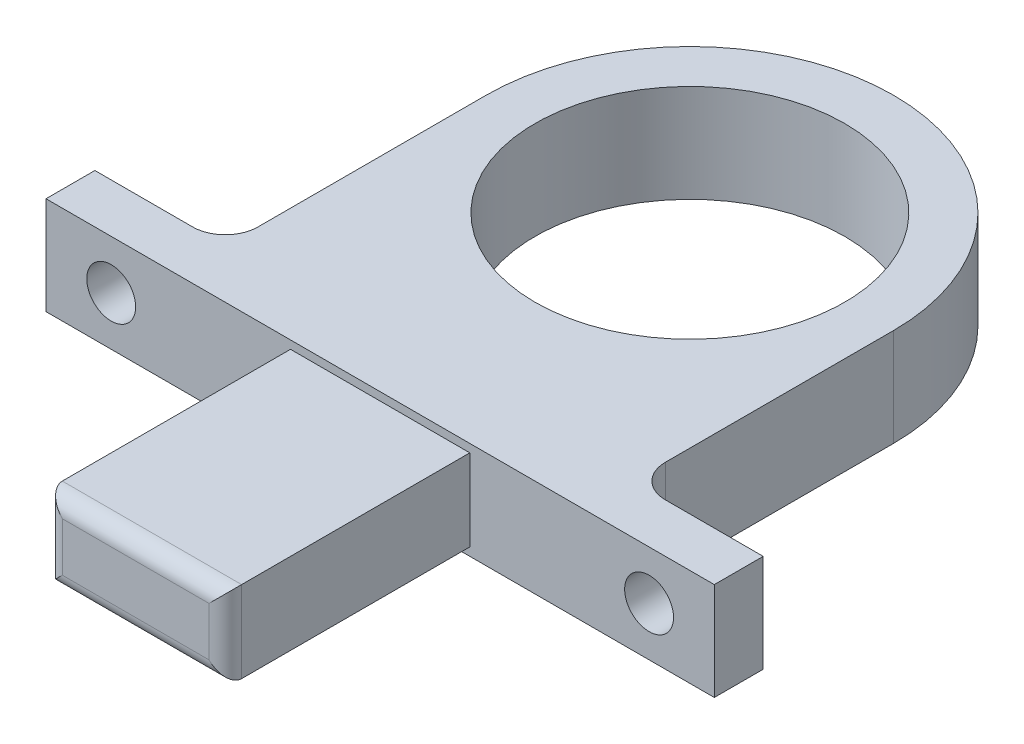
SolidWorks part; units mm, degrees
ref_plane "Alzado" through (0, 0, 0) normal (0, 0, 1) x (1, 0, 0)
ref_plane "Planta" through (0, 0, 0) normal (0, 1, 0) x (1, 0, 0)
ref_plane "Vista lateral" through (0, 0, 0) normal (1, 0, 0) x (0, 0, -1)
sketch "Croquis1" plane through (0, 0, 0) normal (0, 1, 0) x (1, 0, 0)
  line L0 (-12.5, 0) -> (12.5, 0) construction
  line L1 (-12.5, 0) -> (-12.5, -14)
  line L2 (-12.5, -19) -> (12.5, -19)
  line L3 (12.5, -14) -> (12.5, 0)
  line L4 (-20.5, -16) -> (20.5, -16) construction
  line L6 (-20.5, -16) -> (-14.5, -16)
  line L7 (-20.5, -16) -> (-20.5, -19)
  line L8 (-20.5, -19) -> (-12.5, -19)
  line L9 (-12.5, -14) -> (-12.5, -19)
  line L10 (20.5, -16) -> (14.5, -16)
  line L11 (20.5, -16) -> (20.5, -19)
  line L12 (20.5, -19) -> (12.5, -19)
  line L13 (12.5, -14) -> (12.5, -19)
  line L14 (-5.5, -19) -> (5.5, -19)
  line L15 (-5.5, -19) -> (-5.5, -34)
  line L16 (-5.5, -34) -> (5.5, -34)
  line L17 (5.5, -19) -> (5.5, -34)
  circle A0 centre (0, 0) radius 12.5
  circle A1 centre (0, 0) radius 9.5
  arc A2 (14.5, -16) -> (12.5, -14) centre (14.5, -14) cw
  arc A3 (-14.5, -16) -> (-12.5, -14) centre (-14.5, -14) ccw
  dimension "D1" = 25
  dimension "D2" = 19
  dimension "D6" = 2
  dimension "D3" = 19
  dimension "D4" = 3
  dimension "D5" = 8
  dimension "D7" = 8
  dimension "D8" = 25
  dimension "D9" = 12.5
  dimension "D10" = 11
  dimension "D11" = 15
  dimension "D12" = 5.5
extrude "Saliente-Extruir1" add sketch "Croquis1" along normal blind 6 contours A3 L6 L7 L8 L2 L12 L11 L10 A2 L3 A0 L1 | A0 A1 | A3 L6 L7 L8 L9 | L10 A2 L13 L12 L11 | L15 L14 L17 L16 region at (0, 0, 13.9849) region at (0, 0, -12.1464) region at (-16.3773, 0, 17.4328) region at (16.3773, 0, 17.4328)
sketch "Croquis2" plane through (0, 0, 19) normal (0, 0, 1) x (1, 0, 0)
  line L0 (-20.5, 3) -> (20.5, 3) construction
  line L1 (-20.5, 6) -> (-20.5, 0) construction
  line L2 (20.5, 6) -> (20.5, 0) construction
  circle A0 centre (-16.5, 3) radius 1.5
  circle A1 centre (16.5, 3) radius 1.5
  dimension "D3" = 3
  dimension "D4" = 3
  dimension "D1" = 4
  dimension "D2" = 4
extrude "Cortar-Extruir1" cut sketch "Croquis2" against normal blind 6
sketch "Croquis3" plane through (0, 0, 16) normal (0, 0, -1) x (-1, 0, 0)
  circle A0 centre (-16.5, 3) radius 3
  circle A1 centre (16.5, 3) radius 3
  dimension "D1" = 6
  dimension "D2" = 6
extrude "Cortar-Extruir2" cut sketch "Croquis3" along normal blind 6
sketch "Croquis4" plane through (0, 0, 0) normal (0, -1, 0) x (1, 0, 0)
  line L1 (-5.5, 34) -> (5.5, 34)
  line L2 (-5.5, 34) -> (-5.5, 19)
  line L3 (-5.5, 19) -> (5.5, 19)
  line L4 (5.5, 34) -> (5.5, 19)
extrude "Cortar-Extruir3" cut sketch "Croquis4" against normal blind 0.5
sketch "Croquis5" plane through (0, 6, 0) normal (0, 1, 0) x (1, 0, 0)
  line L1 (-5.5, -19) -> (5.5, -19)
  line L2 (-5.5, -19) -> (-5.5, -34)
  line L3 (-5.5, -34) -> (5.5, -34)
  line L4 (5.5, -19) -> (5.5, -34)
extrude "Cortar-Extruir4" cut sketch "Croquis5" against normal blind 0.5
fillet "Redondeo1" radius 1 4 edges at (5.5, 3, 34) (0, 0.5, 34) (-5.5, 3, 34) (0, 5.5, 34)
